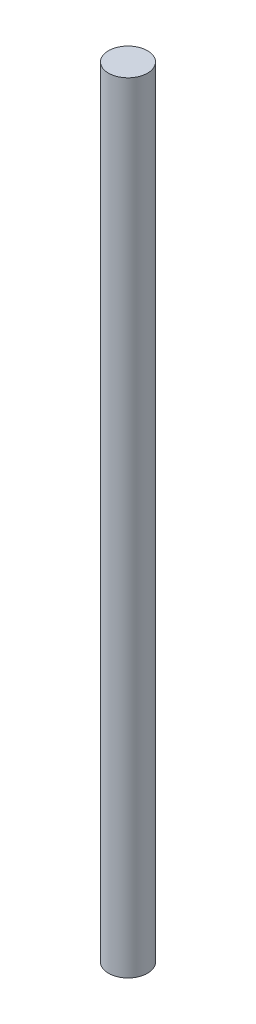
SolidWorks part; units mm, degrees
ref_plane "Front Plane" through (0, 0, 0) normal (0, 0, 1) x (1, 0, 0)
ref_plane "Top Plane" through (0, 0, 0) normal (0, 1, 0) x (1, 0, 0)
ref_plane "Right Plane" through (0, 0, 0) normal (1, 0, 0) x (0, 0, -1)
sketch "Sketch1" plane through (0, 0, 0) normal (0, 1, 0) x (1, 0, 0)
  circle A0 centre (0, 0) radius 6.35
extrude "Boss-Extrude1" add sketch "Sketch1" along normal blind 254
ref_axis "Axis1" through (0, 254, 0) along (0, -1, 0)
